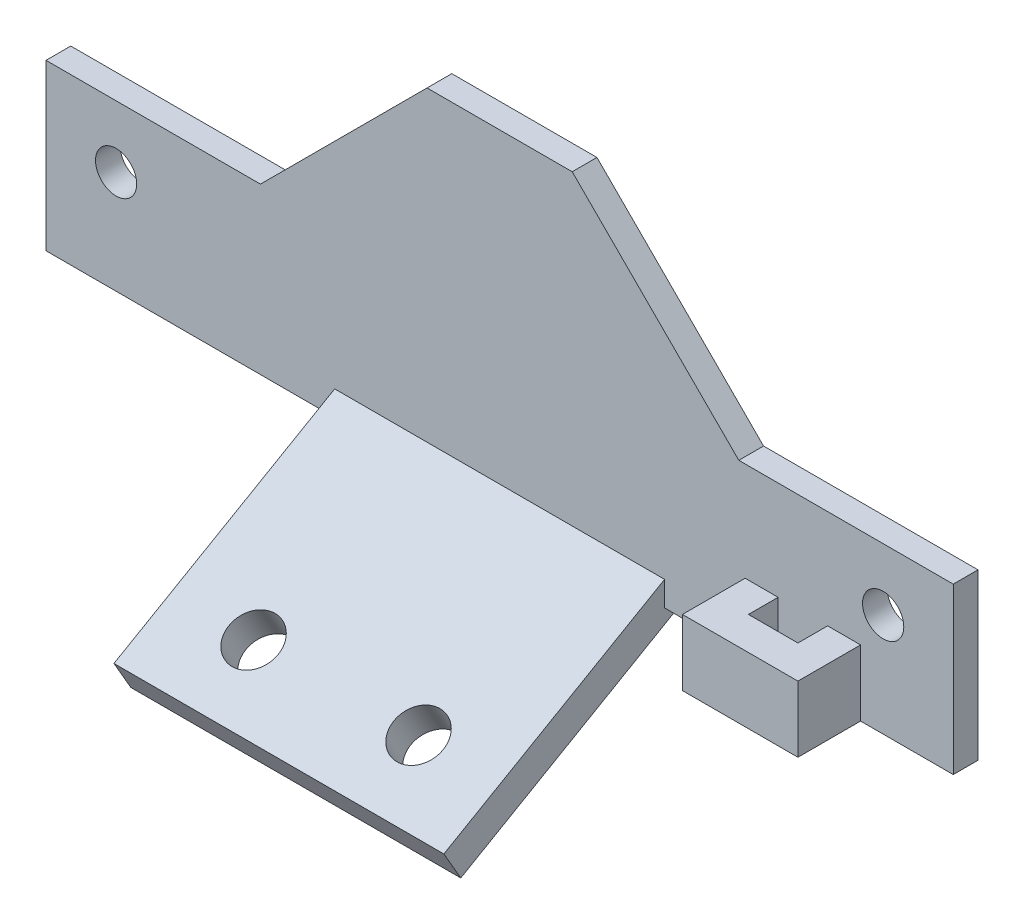
SolidWorks part; units mm, degrees
ref_plane "Alzado" through (0, 0, 0) normal (0, 0, 1) x (1, 0, 0)
ref_plane "Planta" through (0, 0, 0) normal (0, 1, 0) x (1, 0, 0)
ref_plane "Vista lateral" through (0, 0, 0) normal (1, 0, 0) x (0, 0, -1)
sketch "Croquis1" plane through (0, 0, 0) normal (0, 0, 1) x (1, 0, 0)
  line L0 (-68.8373, 14.25) -> (-55.8373, 14.25)
  line L2 (-68.8373, 14.25) -> (-68.8373, 4.25)
  line L3 (-68.8373, 4.25) -> (-13.8373, 4.25)
  line L4 (-13.8373, 14.25) -> (-13.8373, 4.25)
  line L5 (-55.8373, 14.25) -> (-45.7373, 24.35)
  line L6 (-13.8373, 14.25) -> (-26.8373, 14.25)
  line L7 (-26.8373, 14.25) -> (-36.9373, 24.35)
  line L8 (-36.9373, 24.35) -> (-45.7373, 24.35)
  circle A0 centre (-18.0873, 10.5) radius 1.25
  circle A1 centre (-64.5873, 10.5) radius 1.25
  dimension "D4" = 2.5
  dimension "D5" = 2.5
  dimension "D1" = 55
  dimension "D2" = 10
  dimension "D3" = 6.25
  dimension "D6" = 46.5
  dimension "D7" = 4.25
extrude "Saliente-Extruir1" add sketch "Croquis1" along normal blind 1.5
sketch "Croquis2" plane through (-68.8373, 0, 0) normal (-1, 0, 0) x (0, 0, 1)
  line L0 (13.8564, -3.75) -> (14.8809, -1.9755)
  line L1 (0, 4.25) -> (13.8564, -3.75)
  line L2 (1.5, 4.25) -> (1.5, 5.75)
  line L3 (0, 4.25) -> (0, 1.7099) construction
  line L4 (1.5, 14.25) -> (1.5, 4.25) construction
  line L5 (1.5, 5.75) -> (14.8809, -1.9755)
  line L6 (1.5, 4.25) -> (0, 4.25)
  dimension "D1" = 60
  dimension "D2" = 16
extrude "Saliente-Extruir2" add sketch "Croquis2" against normal up to vertex (55 mm away) up to point (-13.8373, 4.25, 1.5)
extrude "Cortar-Extruir1" cut sketch "Croquis2<2>" against normal blind 17.5
sketch "Croquis2<2>" plane through (-68.8373, 0, 0) normal (-1, 0, 0) x (0, 0, 1) same geometry as "Croquis2"
sketch "Croquis3" plane through (-13.8373, 0, 0) normal (1, 0, 0) x (0, 0, -1)
  line L0 (-1.5, 5.75) -> (-14.8809, -1.9755)
  line L1 (-14.8809, -1.9755) -> (-13.8564, -3.75)
  line L2 (-13.8564, -3.75) -> (0, 4.25)
  line L3 (-1.5, 5.75) -> (-1.5, 4.25)
  line L4 (-1.5, 4.25) -> (0, 4.25)
extrude "Cortar-Extruir2" cut sketch "Croquis3" against normal blind 17.5
sketch "Croquis4" plane through (0, 3.1875, 1.8403) normal (0, -0.866, -0.5) x (1, 0, 0)
  line L0 (-51.3373, -2.125) -> (-31.3373, -2.125) construction
  line L1 (-31.3373, 13.875) -> (-31.3373, -2.125) construction
  circle A0 centre (-36.3373, 9.875) radius 1.5
  circle A1 centre (-46.3373, 9.875) radius 1.5
  dimension "D1" = 12
  dimension "D2" = 10
  dimension "D3" = 5
extrude "Cortar-Extruir3" cut sketch "Croquis4" against normal up to vertex (2.049 mm away) up to point (-31.3373, -1.9755, 14.8809)
sketch "Croquis5" plane through (0, 4.25, 0) normal (0, -1, 0) x (1, 0, 0)
  line L0 (-31.3373, 1.5) -> (-13.8373, 1.5) construction
  line L1 (-24.4543, 1.5) -> (-21.4543, 1.5)
  line L2 (-24.4543, 1.5) -> (-24.4543, 3.3)
  line L3 (-24.4543, 3.3) -> (-21.4543, 3.3)
  line L4 (-21.4543, 1.5) -> (-21.4543, 3.3)
  line L5 (-24.4543, 1.5) -> (-26.4543, 1.5)
  line L6 (-26.4543, 1.5) -> (-26.4543, 5.3)
  line L7 (-26.4543, 5.3) -> (-19.4543, 5.3)
  line L8 (-19.4543, 5.3) -> (-19.4543, 1.5)
  line L9 (-19.4543, 1.5) -> (-21.4543, 1.5)
  line M4 (-13.8373, 1.5) -> (-31.3373, 1.5)
  dimension "D1" = 1.8
  dimension "D2" = 3
extrude "Saliente-Extruir3" add sketch "Croquis5" against normal blind 4 contours L8 L7 L6 L2 L3 L4 M4 region at (-22.9543, 4.25, 3.6547)
